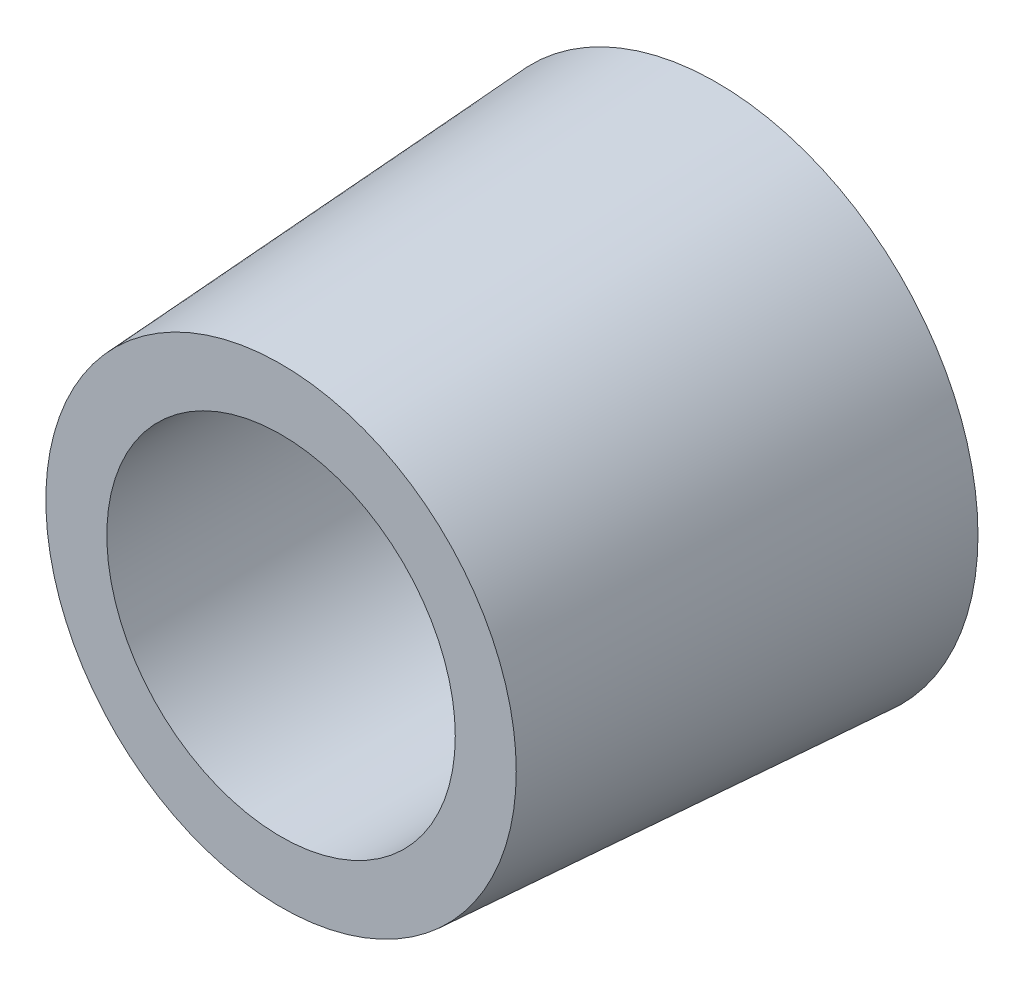
SolidWorks part; units mm, degrees
material "Mosiądz"
ref_plane "Płaszczyzna przednia" through (0, 0, 0) normal (0, 0, 1) x (1, 0, 0)
ref_plane "Płaszczyzna górna" through (0, 0, 0) normal (0, 1, 0) x (1, 0, 0)
ref_plane "Płaszczyzna prawa" through (0, 0, 0) normal (1, 0, 0) x (0, 0, -1)
sketch "Szkic1" plane through (0, 0, 0) normal (0, 0, 1) x (1, 0, 0)
  circle A0 centre (0, 0) radius 3
  dimension "D1" = 6
ref_plane "Płaszczyzna1" through (0, 0, 5) normal (0, 0, 1) x (1, 0, 0)
sketch "Szkic2" plane through (0, 0, 5) normal (0, 0, 1) x (1, 0, 0)
  circle A0 centre (0, 0) radius 2.7
  dimension "D1" = 5.4
loft "Wyciągnięcie po profilach1" add profiles "Szkic1", "Szkic2" connector at (-2.7342, 1.2345, 0) connector at (-2.4187, 1.2, 5)
sketch "Szkic3" plane through (0, 0, 5) normal (0, 0, 1) x (1, 0, 0)
  circle A0 centre (0, 0) radius 2
  dimension "D1" = 4
extrude "Wytnij-wyciągnięcie1" cut sketch "Szkic3" against normal blind 10
